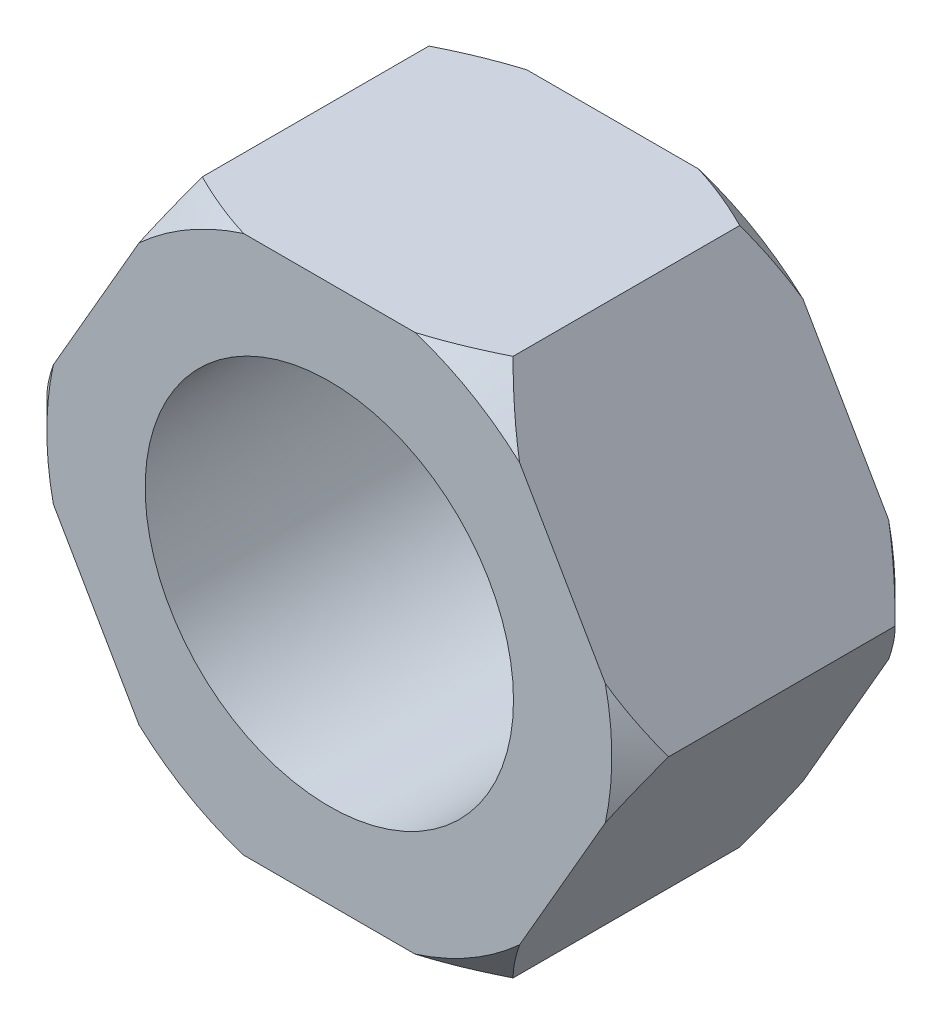
SolidWorks part; units mm, degrees
material "AISI 1045 Steel, cold drawn"
ref_plane "Front Plane" through (0, 0, 0) normal (0, 0, 1) x (1, 0, 0)
ref_plane "Top Plane" through (0, 0, 0) normal (0, 1, 0) x (1, 0, 0)
ref_plane "Right Plane" through (0, 0, 0) normal (1, 0, 0) x (0, 0, -1)
sketch "Sketch1" plane through (0, 0, 0) normal (0, 0, 1) x (1, 0, 0)
  line L1 (10.9697, 0) -> (5.4848, 9.5)
  line L2 (5.4848, 9.5) -> (-5.4848, 9.5)
  line L3 (-5.4848, 9.5) -> (-10.9697, 0)
  line L4 (-10.9697, 0) -> (-5.4848, -9.5)
  line L5 (-5.4848, -9.5) -> (5.4848, -9.5)
  line L6 (5.4848, -9.5) -> (10.9697, 0)
  circle A0 centre (0, 0) radius 6.5
  circle A1 centre (0, 0) radius 9.5 construction
  dimension "D1" = 13
  dimension "D2" = 19
extrude "Boss-Extrude1" add sketch "Sketch1" along normal blind 10
sketch "Sketch2" plane through (0, 0, 0) normal (0, 1, 0) x (0, 0, -1)
  line L0 (-9, 10.9697) -> (-10, 9.9697)
  line L3 (-1, 10.9697) -> (0, 9.9697)
  line L5 (0, 0) -> (-12.4496, 0) construction
  line L6 (-9, 10.9697) -> (-10, 10.9697)
  line L7 (-10, 10.9697) -> (-10, 9.9697)
  line L8 (-1, 10.9697) -> (0, 10.9697)
  line L9 (0, 10.9697) -> (0, 9.9697)
  line L11 (-10, 10.9697) -> (0, 10.9697) construction
  dimension "D1" = 1
revolve "Cut-Revolve3" cut sketch "Sketch2" angle 360 about L5
